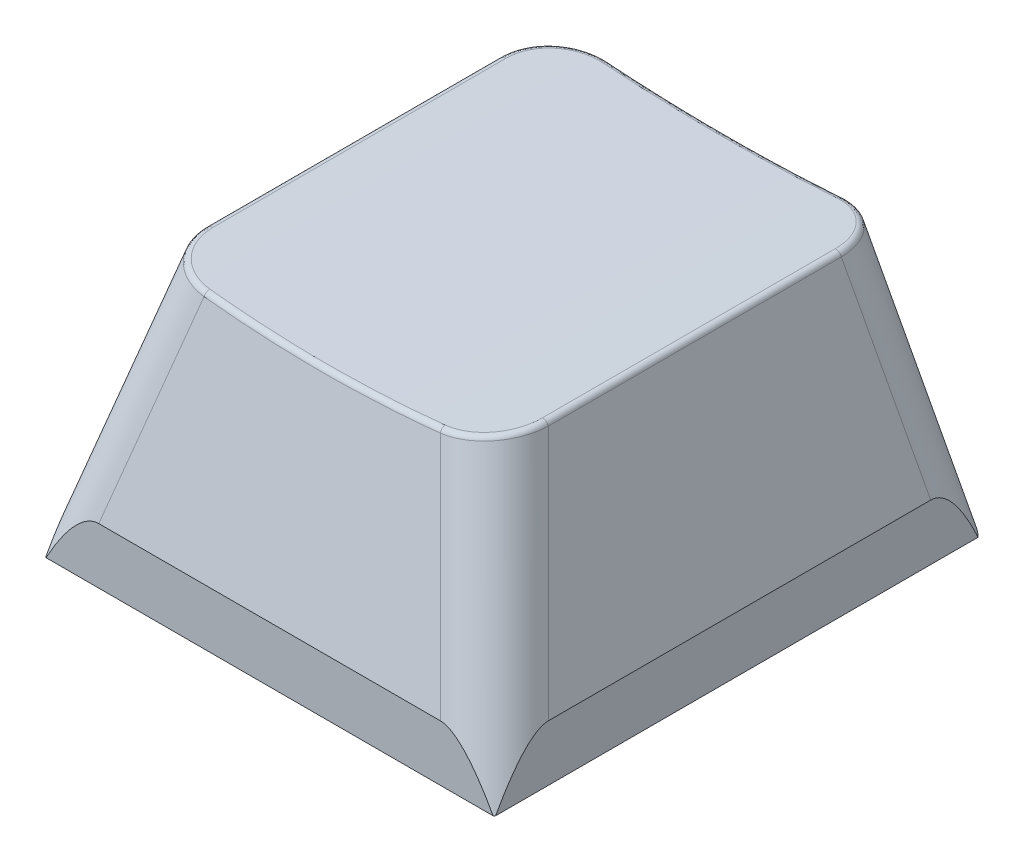
SolidWorks part; units mm, degrees
ref_plane "Front Plane" through (0, 0, 0) normal (0, 0, 1) x (1, 0, 0)
ref_plane "Top Plane" through (0, 0, 0) normal (0, 1, 0) x (1, 0, 0)
ref_plane "Right Plane" through (0, 0, 0) normal (1, 0, 0) x (0, 0, -1)
sketch "Sketch1" plane through (0, 0, 0) normal (0, 1, 0) x (1, 0, 0)
  line L1 (0, 0) -> (11.8, 0)
  line L2 (0, 0) -> (0, 14)
  line L3 (0, 14) -> (11.8, 14)
  line L4 (11.8, 0) -> (11.8, 14)
  dimension "length" = 11.8
  dimension "width" = 14
extrude "Boss-Extrude1" add sketch "Sketch1" along normal blind 8
draft "Draft1" type of draft neutral plane draft angle 15 faces to draft 3 face at (0, 4, -7) face at (11.8, 4, -7) face at (5.9, 4, 0) neutral plane through (0, 8, 0) neutral plane normal (0, 1, 0) parameters "D1"=15
draft "Draft2" type of draft neutral plane draft angle 10 faces to draft 1 face at (5.9, 4, -14) neutral plane through (0, 8, 0) neutral plane normal (0, 1, 0) parameters "D1"=10
sketch "Sketch2" plane through (0, 0, 0) normal (0, -1, 0) x (1, 0, 0)
  line L1 (-2.1436, 2.1436) -> (13.9436, 2.1436)
  line L2 (-2.1436, 2.1436) -> (-2.1436, -15.4106)
  line L3 (-2.1436, -15.4106) -> (13.9436, -15.4106)
  line L4 (13.9436, 2.1436) -> (13.9436, -15.4106)
extrude "Boss-Extrude2" add sketch "Sketch2" along normal blind 2
sketch "Sketch3" plane through (0, 0, 0) normal (0, 0, 1) x (1, 0, 0)
  line L0 (5.9, 8) -> (5.9, 57) construction
  line L2 (0, 8) -> (11.8, 8) construction
  arc A0 (-21.0864, 14.908) -> (50.8896, 35.1841) centre (5.9, 57) ccw
  point P3 (5.9, 32.5)
  dimension "radius" = 50
  dimension "distance" = 49
surface "Surface-Extrude1" sketch "Sketch3" parameters "D1"=58, "D2"=55
other "SurfaceCut1"
fillet "Fillet1" radius 2 4 edges at (12.9562, 3.6848, -14.7609) (-1.1562, 3.6848, -14.7609) (12.9562, 3.6848, 1.1562) (-1.1562, 3.6848, 1.1562)
fillet "Fillet2" radius 0.2 8 edges at (5.9, 7, -14.1763) (11.9689, 7.3697, -6.9673) (-0.1689, 7.3697, -6.9673) (5.9, 7, 0.2679) (0.2755, 7.3174, -0.4833) (11.2708, 7.2893, -0.224) (0.5369, 7.2885, -13.698) (11.5346, 7.3185, -13.4211)
shell "Shell1" thickness 1
